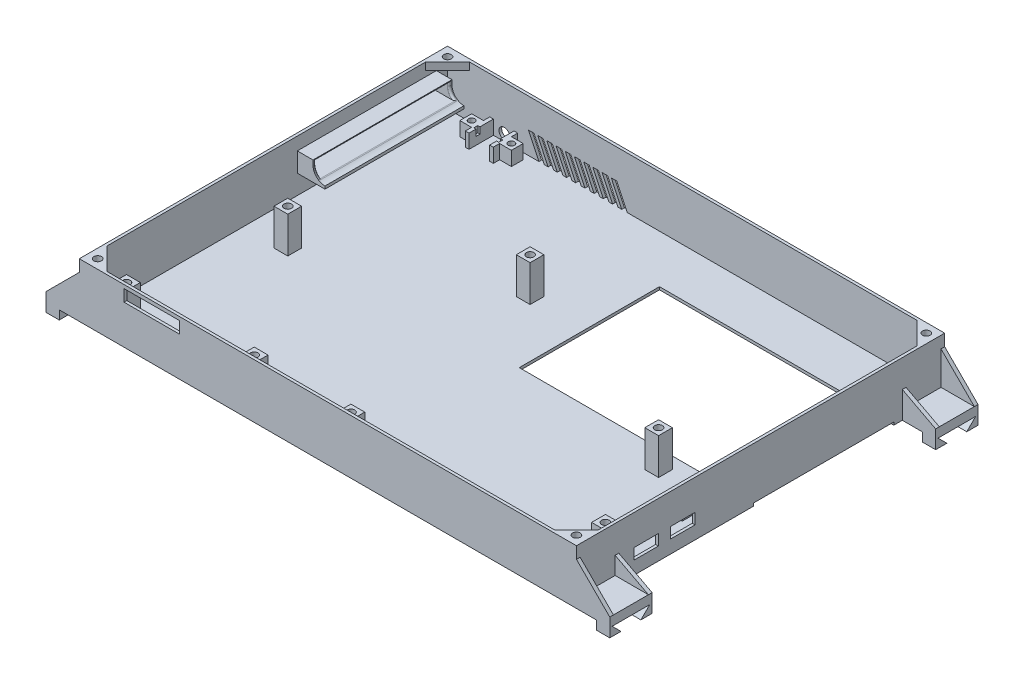
SolidWorks part; units mm, degrees
material "PLA"
ref_plane "Спереди" through (0, 0, 0) normal (0, 0, 1) x (1, 0, 0)
ref_plane "Сверху" through (0, 0, 0) normal (0, 1, 0) x (1, 0, 0)
ref_plane "Справа" through (0, 0, 0) normal (1, 0, 0) x (0, 0, -1)
sketch "Эскиз1" plane through (0, 0, 0) normal (0, 1, 0) x (1, 0, 0)
  line L1 (135, 100) -> (-135, 100)
  line L2 (135, 100) -> (135, -100)
  line L3 (135, -100) -> (-135, -100)
  line L4 (-135, 100) -> (-135, -100)
  line L5 (135, 100) -> (-135, -100) construction
  line L6 (135, -100) -> (-135, 100) construction
  point P0 (0, 0)
  dimension "D1" = 200
  dimension "D2" = 270
extrude "Бобышка-Вытянуть1" add sketch "Эскиз1" along normal blind 1.5
sketch "Эскиз2" plane through (0, 1.5, 0) normal (0, 1, 0) x (1, 0, 0)
  line L0 (133.5, 98.5) -> (-133.5, 98.5)
  line L1 (-133.5, 98.5) -> (-133.5, -98.5)
  line L2 (-133.5, -98.5) -> (-110.7, -98.5)
  line L3 (133.5, -98.5) -> (133.5, 98.5)
  line L4 (-135, 100) -> (-135, -100)
  line L5 (-135, -100) -> (135, -100)
  line L6 (135, -100) -> (135, 100)
  line L7 (135, 100) -> (-135, 100)
  line L8 (-135, 100) -> (-135, -100)
  line L9 (-135, -100) -> (-110.7, -100)
  line L10 (135, -100) -> (135, 100)
  line L11 (135, 100) -> (-135, 100)
  line L12 (-110.7, -98.5) -> (-110.7, -100)
  line L14 (-80.5, -98.5) -> (-80.5, -100)
  line L16 (-80.5, -98.5) -> (133.5, -98.5)
  line L17 (-80.5, -100) -> (135, -100)
  line L18 (-133.5, -98.5) -> (133.5, -98.5) construction
  line L20 (-135, -100) -> (135, -100) construction
  dimension "D3" = 24.3
  dimension "D4" = 54.5
  dimension "D1" = 0
  dimension "D2" = 1.5
extrude "Бобышка-Вытянуть2" add sketch "Эскиз2" along normal offset from surface (28 mm away) 7 offset beyond the face yes
sketch "Эскиз3" plane through (0, 1.5, 0) normal (0, 1, 0) x (1, 0, 0)
  line L1 (-110.7, -98.5) -> (-80.5, -98.5)
  line L2 (-110.7, -98.5) -> (-110.7, -100)
  line L3 (-110.7, -100) -> (-80.5, -100)
  line L4 (-80.5, -98.5) -> (-80.5, -100)
extrude "Бобышка-Вытянуть3" add sketch "Эскиз3" along normal blind 19.7
sketch "Эскиз4" plane through (-110.7, 0, 0) normal (1, 0, 0) x (0, 0, -1)
  line L0 (-100, 29.5) -> (-100, 21.2) construction
  line L1 (-98.5, 29.5) -> (-100, 29.5)
  line L2 (-98.5, 29.5) -> (-98.5, 27.6)
  line L3 (-98.5, 27.6) -> (-100, 27.6)
  line L4 (-100, 29.5) -> (-100, 27.6)
  dimension "D1" = 1.9
extrude "Бобышка-Вытянуть4" add sketch "Эскиз4" along normal up to surface (30.2 mm away) up to face at (-80.5, 25.35, 99.25)
sketch "Эскиз5" plane through (135, 0, 0) normal (1, 0, 0) x (0, 0, -1)
  line L0 (-100, 29.5) -> (-100, 0) construction
  line L1 (-55.55, 13) -> (-68.85, 13)
  line L2 (-55.55, 13) -> (-55.55, 7.1)
  line L3 (-55.55, 7.1) -> (-68.85, 7.1)
  line L4 (-68.85, 13) -> (-68.85, 7.1)
  line L5 (-55.55, 13) -> (-68.85, 7.1) construction
  line L6 (-55.55, 7.1) -> (-68.85, 13) construction
  line L7 (-35.55, 13) -> (-48.85, 13)
  line L8 (-35.55, 13) -> (-35.55, 7.1)
  line L9 (-35.55, 7.1) -> (-48.85, 7.1)
  line L10 (-48.85, 13) -> (-48.85, 7.1)
  line L11 (-35.55, 13) -> (-48.85, 7.1) construction
  line L12 (-35.55, 7.1) -> (-48.85, 13) construction
  line L13 (-100, 0) -> (100, 0) construction
  point P0 (-62.2, 10.05)
  point P5 (-42.2, 10.05)
  dimension "D1" = 13.3
  dimension "D2" = 5.9
  dimension "D3" = 6.7
  dimension "D4" = 31.15
  dimension "D5" = 13
extrude "Вырез-Вытянуть1" cut sketch "Эскиз5" against normal up to surface (1.5 mm away) up to face at (133.5, 15.5, 0)
sketch "Эскиз10" plane through (0, 1.5, 0) normal (0, 1, 0) x (1, 0, 0)
  line L0 (133.5, -14.85) -> (133.5, -98.5) construction
  line L1 (124.175, -24.225) -> (116.675, -24.225)
  line L2 (124.175, -24.225) -> (124.175, -31.725)
  line L3 (124.175, -31.725) -> (116.675, -31.725)
  line L4 (116.675, -24.225) -> (116.675, -31.725)
  line L5 (124.175, -24.225) -> (116.675, -31.725) construction
  line L6 (124.175, -31.725) -> (116.675, -24.225) construction
  line L7 (114.55, -56.3) -> (107.05, -56.3)
  line L8 (114.55, -56.3) -> (114.55, -63.8)
  line L9 (114.55, -63.8) -> (107.05, -63.8)
  line L10 (107.05, -56.3) -> (107.05, -63.8)
  line L11 (114.55, -56.3) -> (107.05, -63.8) construction
  line L12 (114.55, -63.8) -> (107.05, -56.3) construction
  line L13 (115.175, -89.275) -> (107.675, -89.275)
  line L14 (115.175, -89.275) -> (115.175, -96.775)
  line L15 (115.175, -96.775) -> (107.675, -96.775)
  line L16 (107.675, -89.275) -> (107.675, -96.775)
  line L17 (115.175, -89.275) -> (107.675, -96.775) construction
  line L18 (115.175, -96.775) -> (107.675, -89.275) construction
  line L19 (133.5, -98.5) -> (-133.5, -98.5) construction
  point P0 (120.425, -27.975)
  point P5 (110.8, -60.05)
  point P10 (111.425, -93.025)
  dimension "D1" = 13.075
  dimension "D2" = 70.525
  dimension "D3" = 22.7
  dimension "D4" = 38.45
  dimension "D5" = 22.075
  dimension "D6" = 5.475
  dimension "D7" = 7.5
extrude "Бобышка-Вытянуть6" add sketch "Эскиз10" along normal blind 6.9
sketch "Эскиз11" plane through (0, 1.5, 0) normal (0, 1, 0) x (1, 0, 0)
  line L1 (-46.7446, -85.75) -> (-54.2446, -85.75)
  line L2 (-46.7446, -85.75) -> (-46.7446, -93.25)
  line L3 (-46.7446, -93.25) -> (-54.2446, -93.25)
  line L4 (-54.2446, -85.75) -> (-54.2446, -93.25)
  line L5 (-46.7446, -85.75) -> (-54.2446, -93.25) construction
  line L6 (-46.7446, -93.25) -> (-54.2446, -85.75) construction
  line L7 (-19.0224, 28.8491) -> (-26.5224, 28.8491)
  line L8 (-19.0224, 28.8491) -> (-19.0224, 36.3491)
  line L9 (-19.0224, 36.3491) -> (-26.5224, 36.3491)
  line L10 (-26.5224, 28.8491) -> (-26.5224, 36.3491)
  line L11 (-19.0224, 28.8491) -> (-26.5224, 36.3491) construction
  line L12 (-19.0224, 36.3491) -> (-26.5224, 28.8491) construction
  line L13 (-115.5446, -93.8424) -> (-123.0446, -93.8424)
  line L14 (-115.5446, -93.8424) -> (-115.5446, -86.3424)
  line L15 (-115.5446, -86.3424) -> (-123.0446, -86.3424)
  line L16 (-123.0446, -93.8424) -> (-123.0446, -86.3424)
  line L17 (-115.5446, -93.8424) -> (-123.0446, -86.3424) construction
  line L18 (-115.5446, -86.3424) -> (-123.0446, -93.8424) construction
  line L19 (-107.65, -14.1324) -> (-115.15, -14.1324)
  line L20 (-107.65, -14.1324) -> (-107.65, -6.6324)
  line L21 (-107.65, -6.6324) -> (-115.15, -6.6324)
  line L22 (-115.15, -14.1324) -> (-115.15, -6.6324)
  line L23 (-107.65, -14.1324) -> (-115.15, -6.6324) construction
  line L24 (-107.65, -6.6324) -> (-115.15, -14.1324) construction
  line L25 (97.2279, -17.6196) -> (89.7279, -17.6196)
  line L26 (97.2279, -17.6196) -> (97.2279, -10.1196)
  line L27 (97.2279, -10.1196) -> (89.7279, -10.1196)
  line L28 (89.7279, -17.6196) -> (89.7279, -10.1196)
  line L29 (97.2279, -17.6196) -> (89.7279, -10.1196) construction
  line L30 (97.2279, -10.1196) -> (89.7279, -17.6196) construction
  line L31 (94.0554, -99.0196) -> (86.5554, -99.0196)
  line L32 (94.0554, -99.0196) -> (94.0554, -91.5196)
  line L33 (94.0554, -91.5196) -> (86.5554, -91.5196)
  line L34 (86.5554, -99.0196) -> (86.5554, -91.5196)
  line L35 (94.0554, -99.0196) -> (86.5554, -91.5196) construction
  line L36 (94.0554, -91.5196) -> (86.5554, -99.0196) construction
  line L37 (6.3554, -93.8285) -> (-1.1446, -93.8285)
  line L38 (6.3554, -93.8285) -> (6.3554, -86.3285)
  line L39 (6.3554, -86.3285) -> (-1.1446, -86.3285)
  line L40 (-1.1446, -93.8285) -> (-1.1446, -86.3285)
  line L41 (6.3554, -93.8285) -> (-1.1446, -86.3285) construction
  line L42 (6.3554, -86.3285) -> (-1.1446, -93.8285) construction
  line L44 (-133.5, 98.5) -> (133.5, 98.5) construction
  line L45 (-133.5, -98.5) -> (-133.5, 98.5) construction
  line L47 (133.5, -98.5) -> (-133.5, -98.5) construction
  line L48 (133.5, 98.5) -> (133.5, -98.5) construction
  point P0 (-50.4946, -89.5)
  point P5 (-22.7724, 32.5991)
  point P10 (-119.2946, -90.0924)
  point P15 (-111.4, -10.3824)
  point P20 (93.4779, -13.8696)
  point P25 (90.3054, -95.2696)
  point P30 (2.6054, -90.0785)
  dimension "D1" = 7.5
  dimension "D2" = 65.9009
  dimension "D3" = 110.7276
  dimension "D4" = 108.8824
  dimension "D5" = 22.1
  dimension "D6" = 8.4076
  dimension "D7" = 14.2054
  dimension "D8" = 8.4215
  dimension "D9" = 130.8946
  dimension "D10" = 9
  dimension "D11" = 83.0054
  dimension "D12" = 3.2304
  dimension "D13" = 43.1946
  dimension "D14" = 84.6304
  dimension "D15" = 40.0221
extrude "Бобышка-Вытянуть7" add sketch "Эскиз11" along normal blind 19.7
sketch "Эскиз12" plane through (0, 1.5, 0) normal (0, 1, 0) x (1, 0, 0)
  line L1 (135, 72.4) -> (7.7, 72.4)
  line L2 (135, 72.4) -> (135, -3.75)
  line L3 (135, -3.75) -> (7.7, -3.75)
  line L4 (7.7, 72.4) -> (7.7, -3.75)
  line L5 (-133.5, 98.5) -> (133.5, 98.5) construction
  line L6 (135, -100) -> (135, 100) construction
  dimension "D1" = 76.15
  dimension "D2" = 127.3
  dimension "D3" = 26.1
extrude "Вырез-Вытянуть2" cut sketch "Эскиз12" against normal through all
sketch "Эскиз14" plane through (0, 21.2, 0) normal (0, 1, 0) x (1, 0, 0)
  line L0 (-115.15, -6.6324) -> (-107.65, -14.1324) construction
  line L1 (-107.65, -6.6324) -> (-115.15, -14.1324) construction
  line L2 (-19.0224, 36.3491) -> (-26.5224, 28.8491) construction
  line L3 (-26.5224, 36.3491) -> (-19.0224, 28.8491) construction
  line L4 (-123.0446, -86.3424) -> (-115.5446, -93.8424) construction
  line L5 (-115.5446, -86.3424) -> (-123.0446, -93.8424) construction
  line L6 (-54.2446, -85.75) -> (-46.7446, -93.25) construction
  line L7 (-46.7446, -85.75) -> (-54.2446, -93.25) construction
  line L8 (-1.1446, -86.3285) -> (6.3554, -93.8285) construction
  line L9 (6.3554, -86.3285) -> (-1.1446, -93.8285) construction
  line L10 (94.0554, -91.5196) -> (86.5554, -99.0196) construction
  line L11 (94.0554, -91.5196) -> (86.5554, -91.5196) construction
  line L12 (94.0554, -91.5196) -> (94.0554, -99.0196) construction
  line L13 (94.0554, -99.0196) -> (86.5554, -99.0196) construction
  line L14 (86.5554, -91.5196) -> (86.5554, -99.0196) construction
  line L15 (94.0554, -99.0196) -> (86.5554, -91.5196) construction
  line L22 (97.2279, -10.1196) -> (89.7279, -17.6196) construction
  line L23 (97.2279, -17.6196) -> (89.7279, -10.1196) construction
  circle A0 centre (-22.7724, 32.5991) radius 2.05
  circle A1 centre (-111.4, -10.3824) radius 2.05
  circle A2 centre (-119.2946, -90.0924) radius 2.05
  circle A3 centre (-50.4946, -89.5) radius 2.05
  circle A4 centre (2.6054, -90.0785) radius 2.05
  circle A5 centre (90.3054, -95.2696) radius 2.05
  circle A6 centre (93.4779, -13.8696) radius 2.05
  dimension "D1" = 4.1
extrude "Вырез-Вытянуть4" cut sketch "Эскиз14" against normal blind 5
sketch "Эскиз15" plane through (0, 8.4, 0) normal (0, 1, 0) x (1, 0, 0)
  line L0 (124.175, -24.225) -> (116.675, -31.725) construction
  line L1 (116.675, -24.225) -> (124.175, -31.725) construction
  line L2 (107.05, -56.3) -> (114.55, -63.8) construction
  line L3 (114.55, -56.3) -> (107.05, -63.8) construction
  line L4 (107.675, -89.275) -> (115.175, -96.775) construction
  line L5 (115.175, -89.275) -> (107.675, -96.775) construction
  circle A0 centre (111.425, -93.025) radius 2.05
  circle A1 centre (110.8, -60.05) radius 2.05
  circle A2 centre (120.425, -27.975) radius 2.05
  dimension "D1" = 4.1
extrude "Вырез-Вытянуть5" cut sketch "Эскиз15" against normal blind 5
sketch "Эскиз16" plane through (0, 0, -100) normal (0, 0, -1) x (-1, 0, 0)
  line L0 (133.5, 22.5) -> (125, 22.5)
  line L1 (133.5, 29.5) -> (133.5, 1.5) construction
  line L2 (125, 22.5) -> (125, 20)
  line L3 (118.5, 13.5) -> (133.5, 13.5)
  line L4 (133.5, 13.5) -> (133.5, 22.5)
  line L5 (133.5, 1.5) -> (-133.5, 1.5) construction
  arc A0 (125, 20) -> (118.5, 13.5) centre (118.5, 20) cw
  dimension "D3" = 6.5
  dimension "D1" = 8.5
  dimension "D2" = 2.5
  dimension "D4" = 21
  dimension "D5" = 15
extrude "Бобышка-Вытянуть8" add sketch "Эскиз16" against normal blind 75.5 from offset 7.5824 offset against normal yes
sketch "Эскиз18" plane through (0, 0, -16.9176) normal (0, 0, 1) x (1, 0, 0)
  line L0 (-135, 21.5) -> (-125, 21.5)
  line L1 (-135, 29.5) -> (-135, 0) construction
  line L2 (-125, 22.5) -> (-125, 20) construction
  line L3 (-125, 21.5) -> (-125, 20)
  line L4 (-135, 21.5) -> (-135, 14.5)
  line L5 (-135, 14.5) -> (-121.9641, 14.5)
  line L6 (-133.5, 22.5) -> (-125, 22.5) construction
  line L7 (-118.5, 13.5) -> (-133.5, 13.5) construction
  arc A0 (-125, 20) -> (-118.5, 13.5) centre (-118.5, 20) ccw construction
  arc A1 (-125, 20) -> (-121.9641, 14.5) centre (-118.5, 20) ccw
  dimension "D1" = 1
  dimension "D2" = 1
extrude "Вырез-Вытянуть6" cut sketch "Эскиз18" against normal offset from surface (72.5 mm away) 1.5 from offset 1.5 up to face at (-127.3692, 18.1308, -92.4176) offset against normal yes
fillet "Скругление1" radius 1 6 edges at (-125, 20.75, -90.9176) (-125, 20.75, -18.4176) (-124.1906, 16.8589, -90.9176) (-121.9641, 14.5, -54.6676) (-124.1906, 16.8589, -18.4176) (-125, 21.5, -54.6676)
sketch "Эскиз19" plane through (0, 0, -16.9176) normal (0, 0, 1) x (1, 0, 0)
  line L0 (-133.5, 13.5) -> (-133.5, 12)
  line L1 (-133.5, 29.5) -> (-133.5, 1.5) construction
  line L2 (-133.5, 13.5) -> (-118.5, 13.5)
  line L3 (-118.5, 13.5) -> (-133.5, 13.5) construction
  line L4 (-118.5, 13.5) -> (-118.5, 12)
  line L5 (-118.5, 12) -> (-133.5, 12)
  dimension "D1" = 1.5
extrude "Бобышка-Вытянуть9" add sketch "Эскиз19" against normal up to surface (75.5 mm away) up to face at (-127.3692, 18.1308, -92.4176)
sketch "Эскиз20" plane through (0, 0, -100) normal (0, 0, -1) x (-1, 0, 0)
  line L0 (135, 29.5) -> (135, 0) construction
  line L1 (89.5705, 13.5) -> (86.5705, 13.5)
  line L3 (83.9, 1.5) -> (80.9, 1.5)
  line L5 (90.9, 13.5) -> (35.9, 1.5) construction
  line L6 (90.9, 1.5) -> (35.9, 13.5) construction
  line L7 (-135, 0) -> (135, 0) construction
  line L8 (35.9, 1.5) -> (41.5705, 13.5)
  line L9 (44.5705, 13.5) -> (38.9, 1.5)
  line L10 (40.9, 1.5) -> (46.5705, 13.5)
  line L11 (49.5705, 13.5) -> (43.9, 1.5)
  line L12 (45.9, 1.5) -> (51.5705, 13.5)
  line L13 (54.5705, 13.5) -> (48.9, 1.5)
  line L14 (50.9, 1.5) -> (56.5705, 13.5)
  line L15 (59.5705, 13.5) -> (53.9, 1.5)
  line L16 (55.9, 1.5) -> (61.5705, 13.5)
  line L17 (64.5705, 13.5) -> (58.9, 1.5)
  line L18 (60.9, 1.5) -> (66.5705, 13.5)
  line L19 (69.5705, 13.5) -> (63.9, 1.5)
  line L20 (65.9, 1.5) -> (71.5705, 13.5)
  line L21 (74.5705, 13.5) -> (68.9, 1.5)
  line L22 (70.9, 1.5) -> (76.5705, 13.5)
  line L23 (79.5705, 13.5) -> (73.9, 1.5)
  line L24 (75.9, 1.5) -> (81.5705, 13.5)
  line L25 (84.5705, 13.5) -> (78.9, 1.5)
  line L26 (80.9, 1.5) -> (86.5705, 13.5)
  line L27 (89.5705, 13.5) -> (83.9, 1.5)
  line L28 (44.5705, 13.5) -> (41.5705, 13.5)
  line L29 (38.9, 1.5) -> (35.9, 1.5)
  line L30 (43.9, 1.5) -> (40.9, 1.5)
  line L31 (49.5705, 13.5) -> (46.5705, 13.5)
  line L32 (54.5705, 13.5) -> (51.5705, 13.5)
  line L33 (48.9, 1.5) -> (45.9, 1.5)
  line L34 (53.9, 1.5) -> (50.9, 1.5)
  line L35 (59.5705, 13.5) -> (56.5705, 13.5)
  line L36 (58.9, 1.5) -> (55.9, 1.5)
  line L37 (64.5705, 13.5) -> (61.5705, 13.5)
  line L38 (63.9, 1.5) -> (60.9, 1.5)
  line L39 (69.5705, 13.5) -> (66.5705, 13.5)
  line L40 (68.9, 1.5) -> (65.9, 1.5)
  line L41 (74.5705, 13.5) -> (71.5705, 13.5)
  line L42 (73.9, 1.5) -> (70.9, 1.5)
  line L43 (79.5705, 13.5) -> (76.5705, 13.5)
  line L44 (78.9, 1.5) -> (75.9, 1.5)
  line L45 (84.5705, 13.5) -> (81.5705, 13.5)
  line L46 (35.9, 13.5) -> (35.9, 1.5) construction
  line L47 (90.9, 13.5) -> (90.9, 1.5) construction
  point P0 (63.4, 7.5)
  dimension "D1" = 71.6
  dimension "D2" = 1.5
  dimension "D3" = 12
  dimension "D4" = 55
  dimension "D5" = 3
  dimension "D8" = 2
  dimension "D9" = 64.707
  dimension "D6" = 10
extrude "Вырез-Вытянуть7" cut sketch "Эскиз20" against normal up to surface (1.5 mm away) up to face at (0, 15.5, -98.5)
sketch "Эскиз21" plane through (0, 0, -100) normal (0, 0, -1) x (-1, 0, 0)
  line L0 (135, 29.5) -> (135, 0) construction
  line L1 (-135, 0) -> (135, 0) construction
  circle A0 centre (102.7, 5.325) radius 2.9
  dimension "D1" = 5.8
  dimension "D2" = 32.3
  dimension "D3" = 5.325
extrude "Вырез-Вытянуть8" cut sketch "Эскиз21" against normal up to surface (1.5 mm away) up to face at (-57.032, 8.2273, -98.5)
sketch "Эскиз22" plane through (0, 1.5, 0) normal (0, 1, 0) x (1, 0, 0)
  line L0 (-133.5, 98.5) -> (-83.9, 98.5) construction
  line L1 (-108.6, 98.5) -> (-110.6, 98.5)
  line L2 (-108.6, 98.5) -> (-108.6, 85.25)
  line L3 (-108.6, 85.25) -> (-110.6, 85.25)
  line L4 (-110.6, 98.5) -> (-110.6, 85.25)
  line L5 (-133.5, -98.5) -> (-133.5, 98.5) construction
  line L7 (-95.4, 98.5) -> (-97.4, 98.5)
  line L8 (-95.4, 98.5) -> (-95.4, 85.25)
  line L9 (-95.4, 85.25) -> (-97.4, 85.25)
  line L10 (-97.4, 98.5) -> (-97.4, 85.25)
  dimension "D1" = 24.9
  dimension "D2" = 13.25
  dimension "D3" = 2
  dimension "D4" = 36.1
extrude "Бобышка-Вытянуть10" add sketch "Эскиз22" along normal blind 7.65
sketch "Эскиз23" plane through (0, 9.15, 0) normal (0, 1, 0) x (1, 0, 0)
  line L0 (-108.6, 85.25) -> (-108.6, 98.5) construction
  line L1 (-108.6, 91.2) -> (-109.8, 91.2)
  line L2 (-108.6, 91.2) -> (-108.6, 89)
  line L3 (-108.6, 89) -> (-109.8, 89)
  line L4 (-109.8, 91.2) -> (-109.8, 89)
  line L5 (-97.4, 98.5) -> (-97.4, 85.25) construction
  line L6 (-97.4, 91.2) -> (-96.2, 91.2)
  line L7 (-97.4, 91.2) -> (-97.4, 89)
  line L8 (-97.4, 89) -> (-96.2, 89)
  line L9 (-96.2, 91.2) -> (-96.2, 89)
  line L10 (-110.6, 85.25) -> (-108.6, 85.25) construction
  dimension "D1" = 2.2
  dimension "D2" = 1.2
  dimension "D3" = 5.95
extrude "Вырез-Вытянуть9" cut sketch "Эскиз23" against normal blind 3.45
sketch "Эскиз24" plane through (0, 1.5, 0) normal (0, 1, 0) x (1, 0, 0)
  line L0 (-108.6, 91.875) -> (-97.4, 91.875) construction
  line L3 (-103, 91.875) -> (-103, 50091.875) construction
  line L4 (-108.6, 85.25) -> (-108.6, 98.5) construction
  line L5 (-108.6, 98.5) -> (-97.4, 98.5) construction
  line L6 (-110.6, 98.5) -> (-110.6, 85.25) construction
  line L7 (-117, 95.075) -> (-110.6, 95.075)
  line L8 (-117, 95.075) -> (-117, 88.675)
  line L9 (-117, 88.675) -> (-110.6, 88.675)
  line L10 (-110.6, 95.075) -> (-110.6, 88.675)
  line L11 (-117, 95.075) -> (-110.6, 88.675) construction
  line L12 (-117, 88.675) -> (-110.6, 95.075) construction
  line L13 (-89, 88.675) -> (-95.4, 88.675)
  line L14 (-95.4, 95.075) -> (-95.4, 88.675)
  line L15 (-89, 95.075) -> (-95.4, 95.075)
  line L16 (-89, 95.075) -> (-89, 88.675)
  circle A0 centre (-113.8, 91.875) radius 1.7 construction
  point P3 (-108.6, 91.875)
  point P8 (-103, 98.5)
  point P10 (-113.8, 91.875)
  dimension "D1" = 3.4
  dimension "D2" = 1.5
extrude "Бобышка-Вытянуть11" add sketch "Эскиз24" along normal up to surface (7.65 mm away) up to face at (-109.4, 9.15, -90.9875)
sketch "Эскиз25" plane through (0, 9.15, 0) normal (0, 1, 0) x (1, 0, 0)
  line L0 (-117, 95.075) -> (-110.6, 88.675) construction
  line L1 (-110.6, 95.075) -> (-117, 88.675) construction
  line L2 (-95.4, 95.075) -> (-89, 88.675) construction
  line L3 (-89, 95.075) -> (-95.4, 88.675) construction
  circle A0 centre (-113.8, 91.875) radius 1.7
  circle A1 centre (-92.2, 91.875) radius 1.7
  dimension "D1" = 3.4
extrude "Вырез-Вытянуть10" cut sketch "Эскиз25" against normal blind 3
sketch "Эскиз26" plane through (0, 29.5, 0) normal (0, 1, 0) x (1, 0, 0)
  line L0 (0, 0) -> (0, 50000) construction
  line L1 (0, 0) -> (-50000, 0) construction
  line L2 (121.5, 98.5) -> (133.5, 98.5)
  line L3 (-35.9, 98.5) -> (133.5, 98.5) construction
  line L4 (133.5, 98.5) -> (133.5, 86.5)
  line L5 (133.5, 98.5) -> (133.5, -98.5) construction
  line L6 (133.5, 86.5) -> (121.5, 98.5)
  line L7 (133.5, 98.5) -> (127.5, 92.5) construction
  line L8 (133.5, -98.5) -> (133.5, -86.5)
  line L9 (121.5, -98.5) -> (133.5, -98.5)
  line L10 (133.5, -86.5) -> (121.5, -98.5)
  line L11 (-121.5, -98.5) -> (-133.5, -98.5)
  line L12 (-133.5, -86.5) -> (-121.5, -98.5)
  line L13 (-133.5, -98.5) -> (-133.5, -86.5)
  line L14 (-133.5, 98.5) -> (-133.5, 86.5)
  line L15 (-121.5, 98.5) -> (-133.5, 98.5)
  line L16 (-133.5, 86.5) -> (-121.5, 98.5)
  circle A0 centre (130.0102, 95.0102) radius 2.05 construction
  dimension "D1" = 4.1
  dimension "D3" = 1.5
  dimension "D4" = 1.4398
  dimension "D2" = 12
extrude "Бобышка-Вытянуть12" add sketch "Эскиз26" against normal blind 4
sketch "Эскиз27" plane through (0, 29.5, 0) normal (0, 1, 0) x (1, 0, 0)
  line L0 (0, 0) -> (0, 50000) construction
  line L1 (0, 0) -> (-50000, 0) construction
  line L2 (135, 100) -> (127.5, 92.5) construction
  line L3 (121.5, 98.5) -> (133.5, 86.5) construction
  circle A0 centre (130.0102, 95.0102) radius 2.05
  circle A1 centre (130.0102, -95.0102) radius 2.05
  circle A2 centre (-130.0102, -95.0102) radius 2.05
  circle A3 centre (-130.0102, 95.0102) radius 2.05
  dimension "D1" = 4.1
  dimension "D2" = 1.5
extrude "Вырез-Вытянуть11" cut sketch "Эскиз27" against normal up to surface (4 mm away) up to face at (129.5, 25.5, -94.5)
sketch "Эскиз29" plane through (135, 0, 0) normal (1, 0, 0) x (0, 0, -1)
  line L0 (0, 29.5) -> (0, -49970.5) construction
  line L2 (100, 0) -> (77, 0)
  line L3 (100, 0) -> (100, 5)
  line L4 (100, 5) -> (77, 5)
  line L5 (77, 0) -> (77, 5)
  line L9 (-100, 29.5) -> (100, 29.5) construction
  line L10 (-100, 5) -> (-77, 5)
  line L11 (-77, 0) -> (-77, 5)
  line L12 (-100, 0) -> (-77, 0)
  line L13 (-100, 0) -> (-100, 5)
  point P14 (0, 29.5)
  dimension "D1" = 23
  dimension "D2" = 5
extrude "Бобышка-Вытянуть13" add sketch "Эскиз29" along normal blind 18.1
sketch "Эскиз30" plane through (153.1, 0, 0) normal (1, 0, 0) x (0, 0, -1)
  line L0 (0, 29.5) -> (0, -49970.5) construction
  line L1 (-100, 29.5) -> (100, 29.5) construction
  line L2 (98.7, 0) -> (100, 0)
  line L3 (77, 0) -> (100, 0) construction
  line L4 (100, 0) -> (100, -4.8)
  line L5 (100, -4.8) -> (93.9, -4.8)
  line L6 (93.9, -4.8) -> (98.7, 0)
  line L7 (78.3, 0) -> (77, 0)
  line L8 (77, 0) -> (77, -4.8)
  line L9 (77, -4.8) -> (83.1, -4.8)
  line L10 (83.1, -4.8) -> (78.3, 0)
  line L11 (100, 0) -> (100, 5) construction
  line L13 (-77, -4.8) -> (-83.1, -4.8)
  line L14 (-77, 0) -> (-77, -4.8)
  line L15 (-78.3, 0) -> (-77, 0)
  line L16 (-83.1, -4.8) -> (-78.3, 0)
  line L17 (-100, -4.8) -> (-93.9, -4.8)
  line L18 (-100, 0) -> (-100, -4.8)
  line L19 (-98.7, 0) -> (-100, 0)
  line L20 (-93.9, -4.8) -> (-98.7, 0)
  point P4 (0, 29.5)
  point P13 (98.2736, 0)
  point P16 (98.957, 0)
  point P17 (98.301, 0)
  point P18 (100, 0)
  point P21 (77, 0)
  point P22 (0, 0)
  point P23 (75.4995, 0)
  point P26 (0, 0)
  dimension "D1" = 4.8
  dimension "D2" = 6.1
  dimension "D3" = 1.3
extrude "Бобышка-Вытянуть14" add sketch "Эскиз30" against normal blind 7.2
mirror "Зеркальное отражение3" about plane through (0, 0, 0) normal (1, 0, 0) of "Бобышка-Вытянуть13"
mirror "Зеркальное отражение4" about plane through (0, 0, 0) normal (1, 0, 0) of "Бобышка-Вытянуть14"
sketch "Эскиз35" plane through (0, 0, -100) normal (0, 0, -1) x (-1, 0, 0)
  line L0 (153.1, 5) -> (135, 23.1)
  line L1 (135, 29.5) -> (135, 5) construction
  line L2 (135, 23.1) -> (135, 5)
  line L3 (135, 5) -> (153.1, 5)
  dimension "D1" = 45
extrude "Бобышка-Вытянуть15" add sketch "Эскиз35" against normal blind 2
sketch "Эскиз36" plane through (0, 0, -77) normal (0, 0, 1) x (1, 0, 0)
  line L0 (-153.1, 5) -> (-135, 14.5)
  line L1 (-135, 29.5) -> (-135, 5) construction
  line L2 (-135, 14.5) -> (-135, 5)
  line L3 (-135, 5) -> (-153.1, 5)
  point P6 (0, 0)
extrude "Бобышка-Вытянуть16" add sketch "Эскиз36" against normal blind 2
mirror "Зеркальное отражение6" about plane through (0, 0, 0) normal (0, 0, 1) of "Бобышка-Вытянуть16", "Бобышка-Вытянуть15"
mirror "Зеркальное отражение7" about plane through (0, 0, 0) normal (1, 0, 0) of "Зеркальное отражение6"
